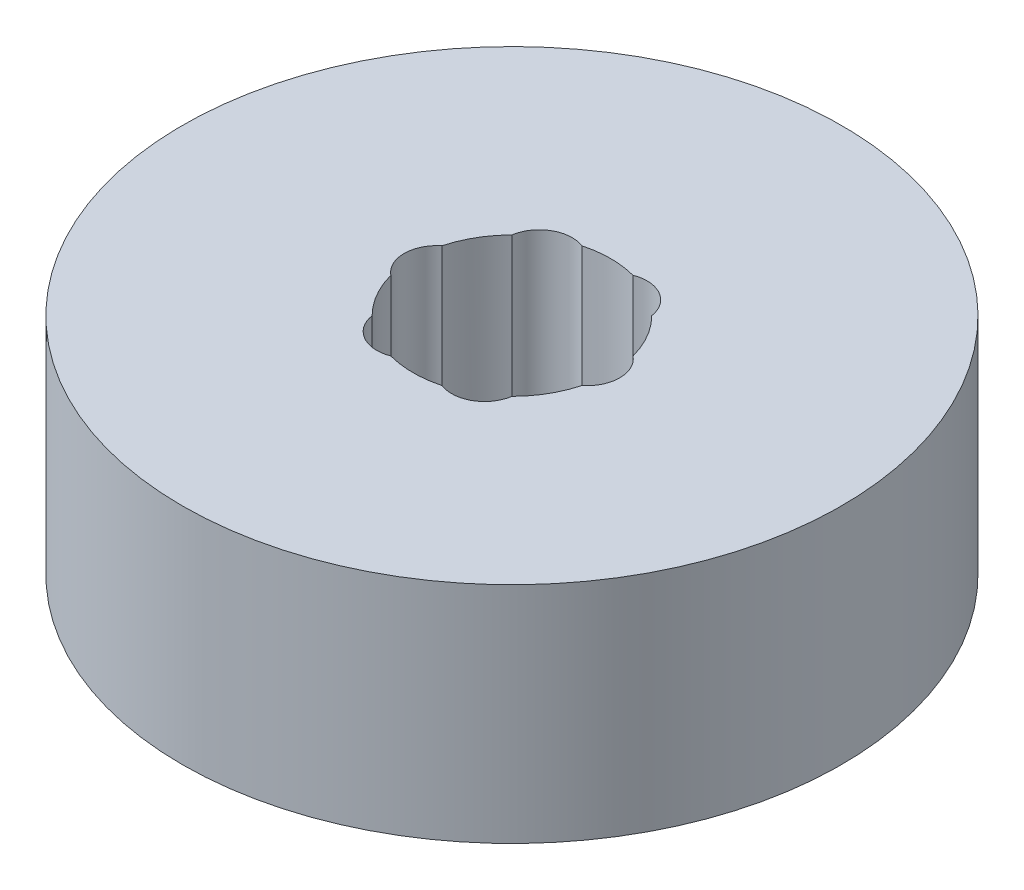
SolidWorks part; units mm, degrees
ref_plane "Front Plane" through (0, 0, 0) normal (0, 0, 1) x (1, 0, 0)
ref_plane "Top Plane" through (0, 0, 0) normal (0, 1, 0) x (1, 0, 0)
ref_plane "Right Plane" through (0, 0, 0) normal (1, 0, 0) x (0, 0, -1)
sketch "Sketch1" plane through (0, 0, 0) normal (0, 1, 0) x (1, 0, 0)
  circle A0 centre (0, 0) radius 25
  dimension "FLANGE_OD" = 50
extrude "Boss-Extrude1" add sketch "Sketch1" along normal blind 17
sketch "Sketch2" plane through (0, 0, 0) normal (0, 1, 0) x (1, 0, 0)
  circle A0 centre (0, 0) radius 7.5
  dimension "BORE_D" = 15
extrude "Cut-Extrude1" cut sketch "Sketch2" along normal through all
sketch "Sketch3" plane through (0, 17, 0) normal (0, 1, 0) x (1, 0, 0)
  circle A0 centre (0, 0) radius 5.6842 construction
  circle A1 centre (-5.6842, 0) radius 2.4908
  dimension "BOLT_D" = 4.9816
  dimension "BOLT_PCD" = 11.3685
extrude "Cut-Extrude2" cut sketch "Sketch3" against normal blind 16.959
pattern_circular "CirPattern1" count 6 over 360 about axis through (0, 0, 0) along (0, 1, 0) of "Cut-Extrude2"
